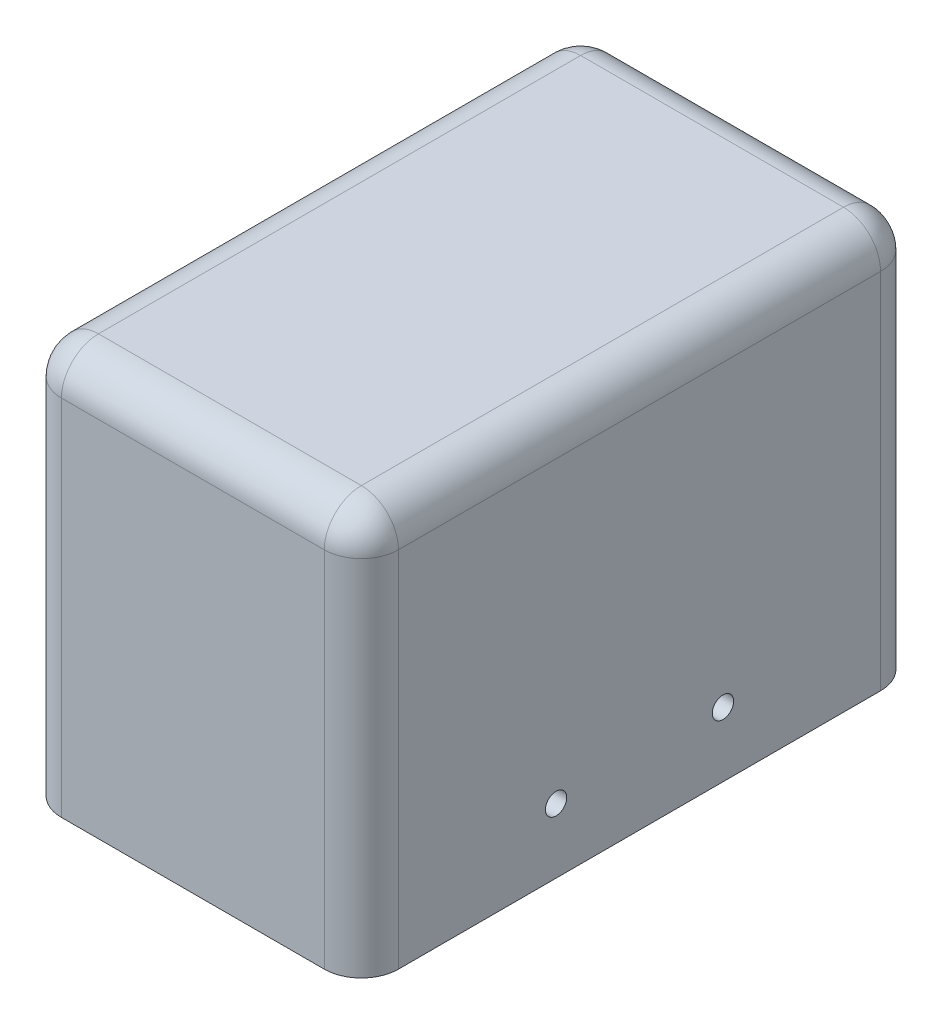
SolidWorks part; units mm, degrees
ref_plane "Front Plane" through (0, 0, 0) normal (0, 0, 1) x (1, 0, 0)
ref_plane "Top Plane" through (0, 0, 0) normal (0, 1, 0) x (1, 0, 0)
ref_plane "Right Plane" through (0, 0, 0) normal (1, 0, 0) x (0, 0, -1)
sketch "Sketch1" plane through (0, 0, 0) normal (0, 1, 0) x (1, 0, 0)
  line L1 (-18.175, 30) -> (18.175, 30)
  line L2 (-18.175, 30) -> (-18.175, -30)
  line L3 (-18.175, -30) -> (18.175, -30)
  line L4 (18.175, 30) -> (18.175, -30)
  line L5 (-18.175, 30) -> (18.175, -30) construction
  line L6 (-18.175, -30) -> (18.175, 30) construction
  line L7 (-15, 26.825) -> (15, 26.825)
  line L8 (-15, 26.825) -> (-15, -26.825)
  line L9 (-15, -26.825) -> (15, -26.825)
  line L10 (15, 26.825) -> (15, -26.825)
  line L11 (-15, 26.825) -> (15, -26.825) construction
  line L12 (-15, -26.825) -> (15, 26.825) construction
  point P0 (0, 0)
  point P6 (0, 0)
  dimension "D1" = 3.175
  dimension "D2" = 3.175
  dimension "D3" = 30
  dimension "D4" = 60
extrude "Boss-Extrude1" add sketch "Sketch1" along normal blind 40
sketch "Sketch2" plane through (0, 40, 0) normal (0, 1, 0) x (1, 0, 0)
  line L1 (-18.175, -30) -> (18.175, -30)
  line L2 (-18.175, -30) -> (-18.175, 30)
  line L3 (-18.175, 30) -> (18.175, 30)
  line L4 (18.175, -30) -> (18.175, 30)
extrude "Boss-Extrude2" add sketch "Sketch2" along normal blind 3.175
fillet "Fillet1" radius 4 8 edges at (-18.175, 43.175, 0) (-18.175, 21.5875, -30) (0, 43.175, -30) (18.175, 21.5875, -30) (18.175, 43.175, 0) (0, 43.175, 30) (18.175, 21.5875, 30) (-18.175, 21.5875, 30)
sketch "Sketch4" plane through (0, 0, 0) normal (0, -1, 0) x (1, 0, 0)
  line L0 (0, 30) -> (0, -30) construction
  line L1 (-14.175, 30) -> (14.175, 30) construction
  line L2 (14.175, -30) -> (-14.175, -30) construction
  line L3 (-18.175, 0) -> (18.175, 0) construction
  line L4 (-18.175, -26) -> (-18.175, 26) construction
  line L5 (18.175, 26) -> (18.175, -26) construction
  line L17 (-3.6, -25) -> (-3.6, -26.825)
  line L18 (15, -26.825) -> (-15, -26.825) construction
  line L19 (3.6, -25) -> (3.6, -26.825)
  line L20 (-3.6, 26.825) -> (3.6, 26.825)
  line L21 (3.6, 25) -> (3.6, 26.825)
  line L22 (-3.6, -26.825) -> (3.6, -26.825)
  line L23 (-3.6, 25) -> (-3.6, 26.825)
  arc A4 (3.6, -25) -> (-3.6, -25) centre (0, -25) ccw
  arc A5 (3.6, 25) -> (-3.6, 25) centre (0, 25) cw
  dimension "D1" = 7.2
  dimension "D2" = 5
extrude "Boss-Extrude3" add sketch "Sketch4" against normal blind 3.5
sketch "Sketch6" plane through (-18.175, 0, 0) normal (-1, 0, 0) x (0, 0, 1)
  line L1 (9, 27.65) -> (15, 27.65)
  line L2 (9, 27.65) -> (9, 24.65)
  line L3 (9, 24.65) -> (15, 24.65)
  line L4 (15, 27.65) -> (15, 24.65)
  line L6 (15, 24.65) -> (15, 27.65) construction
  line L7 (15, 27.65) -> (9, 27.65) construction
  dimension "D1" = 0
  dimension "D2" = 0
  dimension "D3" = 6
  dimension "D4" = 3
extrude "Cut-Extrude3" cut sketch "Sketch6" against normal blind 3.175
sketch "Sketch7" plane through (18.175, 0, 0) normal (1, 0, 0) x (0, 0, -1)
  line L0 (0, 0) -> (0, 43.942) construction
  line L1 (-26, 0) -> (26, 0) construction
  circle A0 centre (-9, 6.97) radius 1.15
  circle A1 centre (9, 6.97) radius 1.15
  dimension "D3" = 2.3
  dimension "D1" = 6.97
  dimension "D2" = 9
extrude "Cut-Extrude4" cut sketch "Sketch7" against normal up to surface (3.175 mm away) up to face at (15, 20, 0)
sketch "Sketch8" plane through (0, 0, 0) normal (0, -1, 0) x (1, 0, 0)
  line L0 (-18.175, 0) -> (18.175, 0) construction
  line L1 (-18.175, -26) -> (-18.175, 26) construction
  line L2 (18.175, 26) -> (18.175, -26) construction
  circle A0 centre (0, -25) radius 3.05
  circle A1 centre (0, 25) radius 3.05
  dimension "D1" = 6.1
extrude "Cut-Extrude5" cut sketch "Sketch8" against normal blind 2.7
